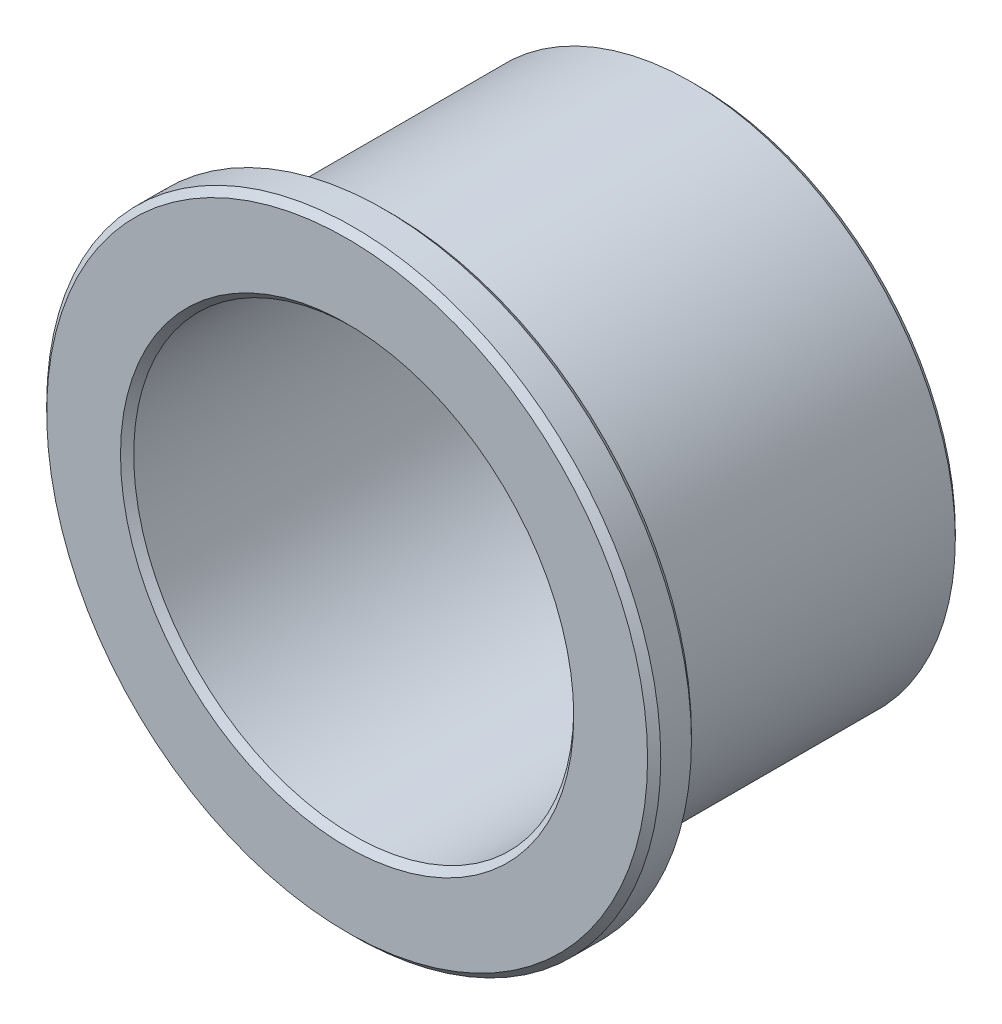
SolidWorks part; units mm, degrees
ref_plane "Front" through (0, 0, 0) normal (0, 0, 1) x (1, 0, 0)
ref_plane "Top" through (0, 0, 0) normal (0, 1, 0) x (1, 0, 0)
ref_plane "Right" through (0, 0, 0) normal (1, 0, 0) x (0, 0, -1)
sketch "Sketch1" plane through (0, 0, 0) normal (0, 0, 1) x (1, 0, 0)
  circle A0 centre (0, 0) radius 7.9629
  circle A1 centre (0, 0) radius 9.5504
  circle A2 centre (0, 0) radius 11.1125
  dimension "ID" = 15.9258
  dimension "OD" = 19.1008
  dimension "Flange OD" = 22.225
sketch "Sketch2" plane through (0, 0, 0) normal (1, 0, 0) x (0, 0, -1)
  line L0 (-6.35, -11.1125) -> (6.35, -11.1125) construction
  line L1 (0, 11.1125) -> (0, -11.1125) construction
  line L3 (-4.7625, 9.5504) -> (6.35, 9.5504) construction
  point P3 (0, -11.1125)
  point P7 (0, 9.5504)
  point P9 (-4.7625, -11.1125)
  point P10 (-6.35, 11.1125)
  point P23 (0, 11.1125)
  dimension "Flange Thickness" = 1.5875
  dimension "Length" = 12.7
sketch "Sketch3" plane through (0, 0, 0) normal (0, 0, 1) x (1, 0, 0)
  circle A0 centre (0, 0) radius 11.1125 construction
  circle A1 centre (0, 0) radius 11.1125
  circle A2 centre (0, 0) radius 7.9629 construction
  circle A3 centre (0, 0) radius 7.9629
extrude "Boss-Extrude1" add sketch "Sketch3" against normal up to vertex (-4.7625 mm away) from vertex up to point (0, -11.1125, 4.7625) starting at point (0, -11.1125, 6.35)
sketch "Sketch4" plane through (0, 0, 0) normal (0, 0, 1) x (1, 0, 0)
  circle A0 centre (0, 0) radius 7.9629 construction
  circle A1 centre (0, 0) radius 9.5504 construction
  circle A2 centre (0, 0) radius 7.9629
  circle A3 centre (0, 0) radius 9.5504
extrude "Boss-Extrude2" add sketch "Sketch4" against normal up to vertex (6.35 mm away) from vertex up to point (0, 9.5504, -6.35) starting at point (0, -11.1125, 4.7625)
chamfer "Chamfer1" distance 0.2389 angle 45 6 edges at (7.9629, 0, 6.35) (11.1125, 0, 6.35) (11.1125, 0, 4.7625) (9.5504, 0, 4.7625) (7.9629, 0, -6.35) (9.5504, 0, -6.35)
equation "\"D1@Chamfer1\"=\"ID@Sketch1\"*0.015"
